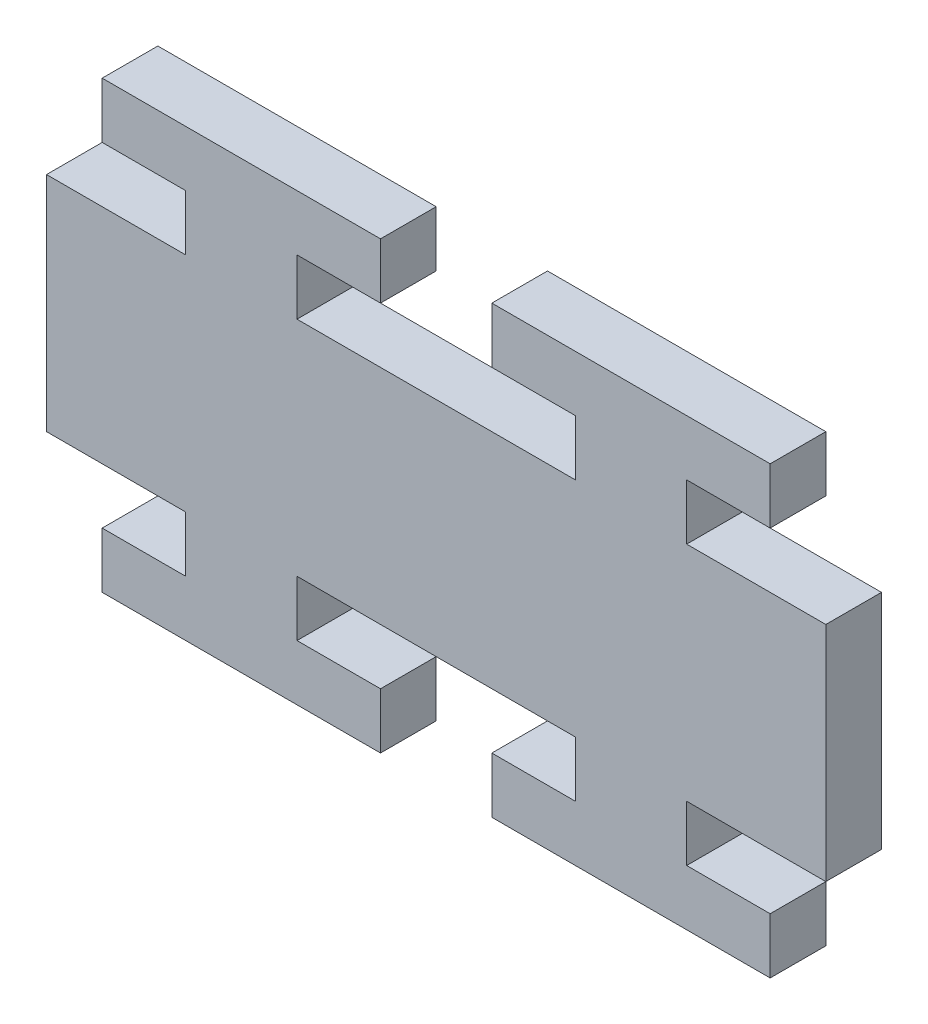
SolidWorks part; units mm, degrees
ref_plane "Plan de face" through (0, 0, 0) normal (0, 0, 1) x (1, 0, 0)
ref_plane "Plan de dessus" through (0, 0, 0) normal (0, 1, 0) x (1, 0, 0)
ref_plane "Plan de droite" through (0, 0, 0) normal (1, 0, 0) x (0, 0, -1)
sketch "Esquisse1" plane through (0, 0, 0) normal (0, 0, 1) x (1, 0, 0)
  line L0 (-35, -10) -> (-22.5, -10)
  line L1 (-35, 10) -> (35, 10) construction
  line L2 (-35, 10) -> (-35, -10)
  line L3 (-35, -10) -> (35, -10) construction
  line L4 (35, 10) -> (35, -10)
  line L5 (-22.5, -10) -> (-22.5, -15)
  line L6 (-22.5, -15) -> (-30, -15)
  line L7 (-30, -15) -> (-30, -20)
  line L8 (-30, -20) -> (-5, -20)
  line L9 (-5, -20) -> (-5, -15)
  line L10 (-5, -15) -> (-12.5, -15)
  line L11 (-12.5, -15) -> (-12.5, -10)
  line L12 (-12.5, -10) -> (12.5, -10)
  line L13 (12.5, -10) -> (12.5, -15)
  line L14 (12.5, -15) -> (5, -15)
  line L15 (5, -15) -> (5, -20)
  line L16 (5, -20) -> (30, -20)
  line L17 (30, -20) -> (30, -15)
  line L18 (30, -15) -> (22.5, -15)
  line L19 (22.5, -15) -> (22.5, -10)
  line L20 (22.5, -10) -> (35, -10)
  line L21 (-35, 10) -> (-22.5, 10)
  line L22 (-22.5, 10) -> (-22.5, 15)
  line L23 (-22.5, 15) -> (-30, 15)
  line L24 (-30, 15) -> (-30, 20)
  line L25 (-30, 20) -> (-5, 20)
  line L26 (-5, 20) -> (-5, 15)
  line L27 (-5, 15) -> (-12.5, 15)
  line L28 (-12.5, 15) -> (-12.5, 10)
  line L29 (-12.5, 10) -> (12.5, 10)
  line L30 (12.5, 10) -> (12.5, 15)
  line L31 (12.5, 15) -> (5, 15)
  line L32 (5, 15) -> (5, 20)
  line L33 (5, 20) -> (30, 20)
  line L34 (30, 20) -> (30, 15)
  line L35 (30, 15) -> (22.5, 15)
  line L36 (22.5, 15) -> (22.5, 10)
  line L37 (22.5, 10) -> (35, 10)
  dimension "D1" = 70
  dimension "D2" = 35
  dimension "D3" = 20
  dimension "D4" = 10
  dimension "D5" = 25
  dimension "D6" = 12.5
  dimension "D7" = 7.5
  dimension "D8" = 5
  dimension "D9" = 5
  dimension "D10" = 5
  dimension "D11" = 7.5
  dimension "D12" = 25
  dimension "D13" = 25
  dimension "D14" = 7.5
  dimension "D15" = 7.5
  dimension "D16" = 5
  dimension "D17" = 5
  dimension "D18" = 5
  dimension "D19" = 5
  dimension "D20" = 5
  dimension "D21" = 5
  dimension "D22" = 5
  dimension "D23" = 5
  dimension "D24" = 5
  dimension "D25" = 12.5
  dimension "D26" = 7.5
  dimension "D27" = 25
  dimension "D28" = 7.5
  dimension "D29" = 25
  dimension "D30" = 7.5
  dimension "D31" = 25
  dimension "D32" = 7.5
extrude "Boss.-Extru.1" add sketch "Esquisse1" along normal blind 5
